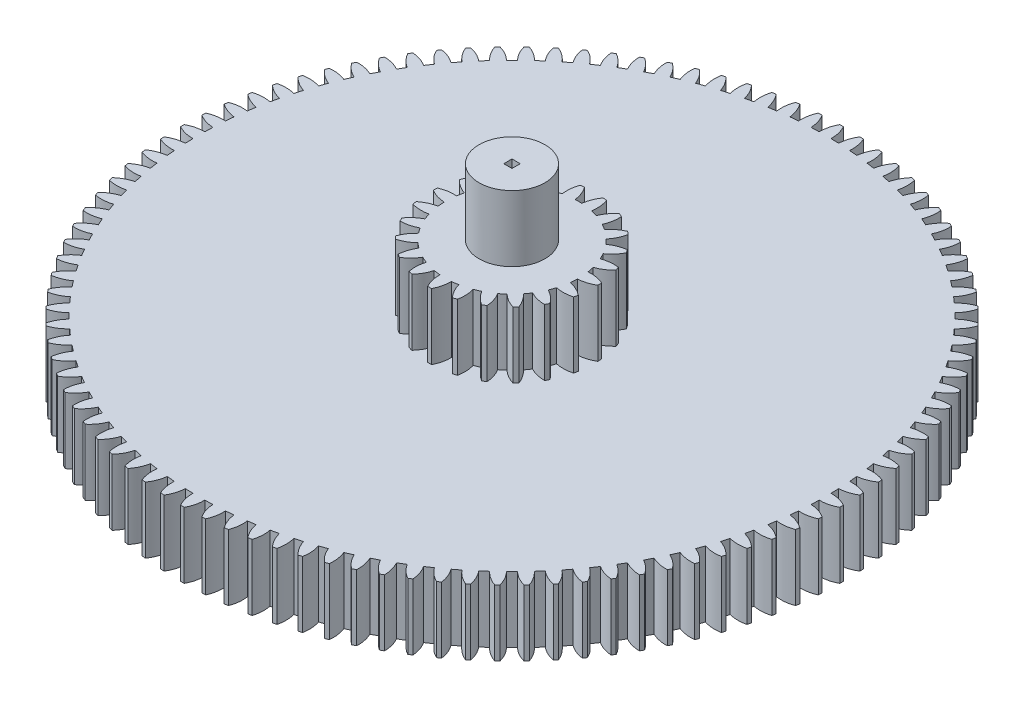
SolidWorks part; units mm, degrees
ref_plane "Front Plane" through (0, 0, 0) normal (0, 0, 1) x (1, 0, 0)
ref_plane "Top Plane" through (0, 0, 0) normal (0, 1, 0) x (1, 0, 0)
ref_plane "Right Plane" through (0, 0, 0) normal (1, 0, 0) x (0, 0, -1)
sketch "Sketch1" plane through (0, 0, 0) normal (0, 1, 0) x (1, 0, 0)
  arc A0 (-1.1228, 2.2337) -> (-1.1773, 2.2054) centre (0, 0) ccw
  arc A1 (-2.1122, 0.8038) -> (-2.1457, 0.7095) centre (0, 0) ccw
  arc A2 (0.05, 2.2594) -> (0.14, 2.4961) centre (0.4546, 2.241) cw
  arc A3 (-0.05, 2.2594) -> (-0.14, 2.4961) centre (-0.4546, 2.241) ccw
  arc A4 (0.3572, 2.2316) -> (0.4786, 2.4538) centre (0.7555, 2.1582) cw
  arc A5 (0.2581, 2.2452) -> (0.2012, 2.4919) centre (-0.1453, 2.282) ccw
  arc A6 (0.6577, 2.1622) -> (0.8082, 2.3657) centre (1.0424, 2.0352) cw
  arc A7 (0.5614, 2.1892) -> (0.5386, 2.4413) centre (0.1668, 2.2805) ccw
  arc A8 (0.946, 2.0525) -> (1.1228, 2.2337) centre (1.3098, 1.8743) cw
  arc A9 (0.8543, 2.0923) -> (0.866, 2.3452) centre (0.4758, 2.2366) ccw
  arc A10 (1.2167, 1.9045) -> (1.4165, 2.06) centre (1.5528, 1.6785) cw
  arc A11 (1.1313, 1.9565) -> (1.1773, 2.2054) centre (0.7759, 2.151) ccw
  arc A12 (1.4647, 1.7211) -> (1.6838, 1.8479) centre (1.7669, 1.4514) cw
  arc A13 (1.3871, 1.7842) -> (1.4666, 2.0246) centre (1.0616, 2.0253) ccw
  arc A14 (1.6854, 1.5057) -> (1.9198, 1.6014) centre (1.9481, 1.1973) cw
  arc A15 (1.6172, 1.5787) -> (1.7287, 1.806) centre (1.3275, 1.8619) ccw
  arc A16 (1.8747, 1.2621) -> (2.12, 1.3251) centre (2.093, 0.9209) cw
  arc A17 (1.8171, 1.3438) -> (1.9585, 1.5538) centre (1.5686, 1.6638) ccw
  arc A18 (2.0291, 0.9951) -> (2.2806, 1.0241) centre (2.1989, 0.6273) cw
  arc A19 (1.9831, 1.0839) -> (2.1518, 1.2727) centre (1.7806, 1.4347) ccw
  arc A20 (2.1457, 0.7095) -> (2.3988, 0.704) centre (2.2638, 0.3221) cw
  arc A21 (2.1122, 0.8038) -> (2.3051, 0.9678) centre (1.9593, 1.1788) ccw
  arc A22 (2.2224, 0.4107) -> (2.4724, 0.3708) centre (2.2866, 0.0108) cw
  arc A23 (2.202, 0.5087) -> (2.4154, 0.6449) centre (2.1016, 0.9011) ccw
  arc A24 (2.2576, 0.1043) -> (2.4998, 0.0307) centre (2.2668, -0.3006) cw
  arc A25 (2.2508, 0.2041) -> (2.4807, 0.31) centre (2.2047, 0.6065) ccw
  arc A26 (2.2508, -0.2041) -> (2.4807, -0.31) centre (2.2047, -0.6065) cw
  arc A27 (2.2576, -0.1043) -> (2.4998, -0.0307) centre (2.2668, 0.3006) ccw
  arc A28 (2.202, -0.5087) -> (2.4154, -0.6449) centre (2.1016, -0.9011) cw
  arc A29 (2.2224, -0.4107) -> (2.4724, -0.3708) centre (2.2866, -0.0108) ccw
  arc A30 (2.1122, -0.8038) -> (2.3051, -0.9678) centre (1.9593, -1.1788) cw
  arc A31 (2.1457, -0.7095) -> (2.3988, -0.704) centre (2.2638, -0.3221) ccw
  arc A32 (1.9831, -1.0839) -> (2.1518, -1.2727) centre (1.7806, -1.4347) cw
  arc A33 (2.0291, -0.9951) -> (2.2806, -1.0241) centre (2.1989, -0.6273) ccw
  arc A34 (1.8171, -1.3438) -> (1.9585, -1.5538) centre (1.5686, -1.6638) cw
  arc A35 (1.8747, -1.2621) -> (2.12, -1.3251) centre (2.093, -0.9209) ccw
  arc A36 (1.6172, -1.5787) -> (1.7287, -1.806) centre (1.3275, -1.8619) cw
  arc A37 (1.6854, -1.5057) -> (1.9198, -1.6014) centre (1.9481, -1.1973) ccw
  arc A38 (1.3871, -1.7842) -> (1.4666, -2.0246) centre (1.0616, -2.0253) cw
  arc A39 (1.4647, -1.7211) -> (1.6838, -1.8479) centre (1.7669, -1.4514) ccw
  arc A40 (1.1313, -1.9565) -> (1.1773, -2.2054) centre (0.7759, -2.151) cw
  arc A41 (1.2167, -1.9045) -> (1.4165, -2.06) centre (1.5528, -1.6785) ccw
  arc A42 (0.8543, -2.0923) -> (0.866, -2.3452) centre (0.4758, -2.2366) cw
  arc A43 (0.946, -2.0525) -> (1.1228, -2.2337) centre (1.3098, -1.8743) ccw
  arc A44 (0.5614, -2.1892) -> (0.5386, -2.4413) centre (0.1668, -2.2805) cw
  arc A45 (0.6577, -2.1622) -> (0.8082, -2.3657) centre (1.0424, -2.0352) ccw
  arc A46 (0.2581, -2.2452) -> (0.2012, -2.4919) centre (-0.1453, -2.282) cw
  arc A47 (0.3572, -2.2316) -> (0.4786, -2.4538) centre (0.7555, -2.1582) ccw
  arc A48 (-0.05, -2.2594) -> (-0.14, -2.4961) centre (-0.4546, -2.241) cw
  arc A49 (0.05, -2.2594) -> (0.14, -2.4961) centre (0.4546, -2.241) ccw
  arc A50 (-0.3572, -2.2316) -> (-0.4786, -2.4538) centre (-0.7555, -2.1582) cw
  arc A51 (-0.2581, -2.2452) -> (-0.2012, -2.4919) centre (0.1453, -2.282) ccw
  arc A52 (-0.6577, -2.1622) -> (-0.8082, -2.3657) centre (-1.0424, -2.0352) cw
  arc A53 (-0.5614, -2.1892) -> (-0.5386, -2.4413) centre (-0.1668, -2.2805) ccw
  arc A54 (-0.946, -2.0525) -> (-1.1228, -2.2337) centre (-1.3098, -1.8743) cw
  arc A55 (-0.8543, -2.0923) -> (-0.866, -2.3452) centre (-0.4758, -2.2366) ccw
  arc A56 (-1.2167, -1.9045) -> (-1.4165, -2.06) centre (-1.5528, -1.6785) cw
  arc A57 (-1.1313, -1.9565) -> (-1.1773, -2.2054) centre (-0.7759, -2.151) ccw
  arc A58 (-1.4647, -1.7211) -> (-1.6838, -1.8479) centre (-1.7669, -1.4514) cw
  arc A59 (-1.3871, -1.7842) -> (-1.4666, -2.0246) centre (-1.0616, -2.0253) ccw
  arc A60 (-1.6854, -1.5057) -> (-1.9198, -1.6014) centre (-1.9481, -1.1973) cw
  arc A61 (-1.6172, -1.5787) -> (-1.7287, -1.806) centre (-1.3275, -1.8619) ccw
  arc A62 (-1.8747, -1.2621) -> (-2.12, -1.3251) centre (-2.093, -0.9209) cw
  arc A63 (-1.8171, -1.3438) -> (-1.9585, -1.5538) centre (-1.5686, -1.6638) ccw
  arc A64 (-2.0291, -0.9951) -> (-2.2806, -1.0241) centre (-2.1989, -0.6273) cw
  arc A65 (-1.9831, -1.0839) -> (-2.1518, -1.2727) centre (-1.7806, -1.4347) ccw
  arc A66 (-2.1457, -0.7095) -> (-2.3988, -0.704) centre (-2.2638, -0.3221) cw
  arc A67 (-2.1122, -0.8038) -> (-2.3051, -0.9678) centre (-1.9593, -1.1788) ccw
  arc A68 (-2.2224, -0.4107) -> (-2.4724, -0.3708) centre (-2.2866, -0.0108) cw
  arc A69 (-2.202, -0.5087) -> (-2.4154, -0.6449) centre (-2.1016, -0.9011) ccw
  arc A70 (-2.2576, -0.1043) -> (-2.4998, -0.0307) centre (-2.2668, 0.3006) cw
  arc A71 (-2.2508, -0.2041) -> (-2.4807, -0.31) centre (-2.2047, -0.6065) ccw
  arc A72 (-2.2508, 0.2041) -> (-2.4807, 0.31) centre (-2.2047, 0.6065) cw
  arc A73 (-2.2576, 0.1043) -> (-2.4998, 0.0307) centre (-2.2668, -0.3006) ccw
  arc A74 (-2.202, 0.5087) -> (-2.4154, 0.6449) centre (-2.1016, 0.9011) cw
  arc A75 (-2.2224, 0.4107) -> (-2.4724, 0.3708) centre (-2.2866, 0.0108) ccw
  arc A76 (-2.1122, 0.8038) -> (-2.3051, 0.9678) centre (-1.9593, 1.1788) cw
  arc A77 (-2.1457, 0.7095) -> (-2.3988, 0.704) centre (-2.2638, 0.3221) ccw
  arc A78 (-1.9831, 1.0839) -> (-2.1518, 1.2727) centre (-1.7806, 1.4347) cw
  arc A79 (-2.0291, 0.9951) -> (-2.2806, 1.0241) centre (-2.1989, 0.6273) ccw
  arc A80 (-1.8171, 1.3438) -> (-1.9585, 1.5538) centre (-1.5686, 1.6638) cw
  arc A81 (-1.8747, 1.2621) -> (-2.12, 1.3251) centre (-2.093, 0.9209) ccw
  arc A82 (-1.6172, 1.5787) -> (-1.7287, 1.806) centre (-1.3275, 1.8619) cw
  arc A83 (-1.6854, 1.5057) -> (-1.9198, 1.6014) centre (-1.9481, 1.1973) ccw
  arc A84 (-1.3871, 1.7842) -> (-1.4666, 2.0246) centre (-1.0616, 2.0253) cw
  arc A85 (-1.4647, 1.7211) -> (-1.6838, 1.8479) centre (-1.7669, 1.4514) ccw
  arc A86 (-1.1313, 1.9565) -> (-1.1773, 2.2054) centre (-0.7759, 2.151) cw
  arc A87 (-1.2167, 1.9045) -> (-1.4165, 2.06) centre (-1.5528, 1.6785) ccw
  arc A88 (-0.8543, 2.0923) -> (-0.866, 2.3452) centre (-0.4758, 2.2366) cw
  arc A89 (-0.946, 2.0525) -> (-1.1228, 2.2337) centre (-1.3098, 1.8743) ccw
  arc A90 (-0.5614, 2.1892) -> (-0.5386, 2.4413) centre (-0.1668, 2.2805) cw
  arc A91 (-0.6577, 2.1622) -> (-0.8082, 2.3657) centre (-1.0424, 2.0352) ccw
  arc A92 (-0.2581, 2.2452) -> (-0.2012, 2.4919) centre (0.1453, 2.282) cw
  arc A93 (-0.3572, 2.2316) -> (-0.4786, 2.4538) centre (-0.7555, 2.1582) ccw
  arc A94 (-1.4165, 2.06) -> (-1.4666, 2.0246) centre (0, 0) ccw
  arc A95 (-1.6838, 1.8479) -> (-1.7287, 1.806) centre (0, 0) ccw
  arc A96 (-1.9198, 1.6014) -> (-1.9585, 1.5538) centre (0, 0) ccw
  arc A97 (-2.12, 1.3251) -> (-2.1518, 1.2727) centre (0, 0) ccw
  arc A98 (-2.2806, 1.0241) -> (-2.3051, 0.9678) centre (0, 0) ccw
  arc A99 (-2.3988, 0.704) -> (-2.4154, 0.6449) centre (0, 0) ccw
  arc A100 (-2.4724, 0.3708) -> (-2.4807, 0.31) centre (0, 0) ccw
  arc A101 (-2.4998, 0.0307) -> (-2.4998, -0.0307) centre (0, 0) ccw
  arc A102 (-2.4807, -0.31) -> (-2.4724, -0.3708) centre (0, 0) ccw
  arc A103 (-2.4154, -0.6449) -> (-2.3988, -0.704) centre (0, 0) ccw
  arc A104 (-2.3051, -0.9678) -> (-2.2806, -1.0241) centre (0, 0) ccw
  arc A105 (-2.1518, -1.2727) -> (-2.12, -1.3251) centre (0, 0) ccw
  arc A106 (-1.9585, -1.5538) -> (-1.9198, -1.6014) centre (0, 0) ccw
  arc A107 (-1.7287, -1.806) -> (-1.6838, -1.8479) centre (0, 0) ccw
  arc A108 (-1.4666, -2.0246) -> (-1.4165, -2.06) centre (0, 0) ccw
  arc A109 (-1.1773, -2.2054) -> (-1.1228, -2.2337) centre (0, 0) ccw
  arc A110 (-0.866, -2.3452) -> (-0.8082, -2.3657) centre (0, 0) ccw
  arc A111 (-0.5386, -2.4413) -> (-0.4786, -2.4538) centre (0, 0) ccw
  arc A112 (-0.2012, -2.4919) -> (-0.14, -2.4961) centre (0, 0) ccw
  arc A113 (0.14, -2.4961) -> (0.2012, -2.4919) centre (0, 0) ccw
  arc A114 (0.4786, -2.4538) -> (0.5386, -2.4413) centre (0, 0) ccw
  arc A115 (0.8082, -2.3657) -> (0.866, -2.3452) centre (0, 0) ccw
  arc A116 (1.1228, -2.2337) -> (1.1773, -2.2054) centre (0, 0) ccw
  arc A117 (1.4165, -2.06) -> (1.4666, -2.0246) centre (0, 0) ccw
  arc A118 (1.6838, -1.8479) -> (1.7287, -1.806) centre (0, 0) ccw
  arc A119 (1.9198, -1.6014) -> (1.9585, -1.5538) centre (0, 0) ccw
  arc A120 (2.12, -1.3251) -> (2.1518, -1.2727) centre (0, 0) ccw
  arc A121 (2.2806, -1.0241) -> (2.3051, -0.9678) centre (0, 0) ccw
  arc A122 (2.3988, -0.704) -> (2.4154, -0.6449) centre (0, 0) ccw
  arc A123 (2.4724, -0.3708) -> (2.4807, -0.31) centre (0, 0) ccw
  arc A124 (2.4998, -0.0307) -> (2.4998, 0.0307) centre (0, 0) ccw
  arc A125 (2.4807, 0.31) -> (2.4724, 0.3708) centre (0, 0) ccw
  arc A126 (2.4154, 0.6449) -> (2.3988, 0.704) centre (0, 0) ccw
  arc A127 (2.3051, 0.9678) -> (2.2806, 1.0241) centre (0, 0) ccw
  arc A128 (2.1518, 1.2727) -> (2.12, 1.3251) centre (0, 0) ccw
  arc A129 (1.9585, 1.5538) -> (1.9198, 1.6014) centre (0, 0) ccw
  arc A130 (1.7287, 1.806) -> (1.6838, 1.8479) centre (0, 0) ccw
  arc A131 (1.4666, 2.0246) -> (1.4165, 2.06) centre (0, 0) ccw
  arc A132 (1.1773, 2.2054) -> (1.1228, 2.2337) centre (0, 0) ccw
  arc A133 (0.866, 2.3452) -> (0.8082, 2.3657) centre (0, 0) ccw
  arc A134 (0.5386, 2.4413) -> (0.4786, 2.4538) centre (0, 0) ccw
  arc A135 (0.2012, 2.4919) -> (0.14, 2.4961) centre (0, 0) ccw
  arc A136 (-0.14, 2.4961) -> (-0.2012, 2.4919) centre (0, 0) ccw
  arc A137 (-0.4786, 2.4538) -> (-0.5386, 2.4413) centre (0, 0) ccw
  arc A138 (-0.8082, 2.3657) -> (-0.866, 2.3452) centre (0, 0) ccw
  arc A139 (-2.202, 0.5087) -> (-2.2224, 0.4107) centre (0, 0) ccw
  arc A140 (-2.2508, 0.2041) -> (-2.2576, 0.1043) centre (0, 0) ccw
  arc A141 (-2.2576, -0.1043) -> (-2.2508, -0.2041) centre (0, 0) ccw
  arc A142 (-2.2224, -0.4107) -> (-2.202, -0.5087) centre (0, 0) ccw
  arc A143 (-2.1457, -0.7095) -> (-2.1122, -0.8038) centre (0, 0) ccw
  arc A144 (-2.0291, -0.9951) -> (-1.9831, -1.0839) centre (0, 0) ccw
  arc A145 (-1.8747, -1.2621) -> (-1.8171, -1.3438) centre (0, 0) ccw
  arc A146 (-1.6854, -1.5057) -> (-1.6172, -1.5787) centre (0, 0) ccw
  arc A147 (-1.4647, -1.7211) -> (-1.3871, -1.7842) centre (0, 0) ccw
  arc A148 (-1.2167, -1.9045) -> (-1.1313, -1.9565) centre (0, 0) ccw
  arc A149 (-0.946, -2.0525) -> (-0.8543, -2.0923) centre (0, 0) ccw
  arc A150 (-0.6577, -2.1622) -> (-0.5614, -2.1892) centre (0, 0) ccw
  arc A151 (-0.3572, -2.2316) -> (-0.2581, -2.2452) centre (0, 0) ccw
  arc A152 (-0.05, -2.2594) -> (0.05, -2.2594) centre (0, 0) ccw
  arc A153 (0.2581, -2.2452) -> (0.3572, -2.2316) centre (0, 0) ccw
  arc A154 (0.5614, -2.1892) -> (0.6577, -2.1622) centre (0, 0) ccw
  arc A155 (0.8543, -2.0923) -> (0.946, -2.0525) centre (0, 0) ccw
  arc A156 (1.1313, -1.9565) -> (1.2167, -1.9045) centre (0, 0) ccw
  arc A157 (1.3871, -1.7842) -> (1.4647, -1.7211) centre (0, 0) ccw
  arc A158 (1.6172, -1.5787) -> (1.6854, -1.5057) centre (0, 0) ccw
  arc A159 (1.8171, -1.3438) -> (1.8747, -1.2621) centre (0, 0) ccw
  arc A160 (1.9831, -1.0839) -> (2.0291, -0.9951) centre (0, 0) ccw
  arc A161 (2.1122, -0.8038) -> (2.1457, -0.7095) centre (0, 0) ccw
  arc A162 (2.202, -0.5087) -> (2.2224, -0.4107) centre (0, 0) ccw
  arc A163 (2.2508, -0.2041) -> (2.2576, -0.1043) centre (0, 0) ccw
  arc A164 (2.2576, 0.1043) -> (2.2508, 0.2041) centre (0, 0) ccw
  arc A165 (2.2224, 0.4107) -> (2.202, 0.5087) centre (0, 0) ccw
  arc A166 (2.1457, 0.7095) -> (2.1122, 0.8038) centre (0, 0) ccw
  arc A167 (2.0291, 0.9951) -> (1.9831, 1.0839) centre (0, 0) ccw
  arc A168 (1.8747, 1.2621) -> (1.8171, 1.3438) centre (0, 0) ccw
  arc A169 (1.6854, 1.5057) -> (1.6172, 1.5787) centre (0, 0) ccw
  arc A170 (1.4647, 1.7211) -> (1.3871, 1.7842) centre (0, 0) ccw
  arc A171 (1.2167, 1.9045) -> (1.1313, 1.9565) centre (0, 0) ccw
  arc A172 (0.946, 2.0525) -> (0.8543, 2.0923) centre (0, 0) ccw
  arc A173 (0.6577, 2.1622) -> (0.5614, 2.1892) centre (0, 0) ccw
  arc A174 (0.3572, 2.2316) -> (0.2581, 2.2452) centre (0, 0) ccw
  arc A175 (0.05, 2.2594) -> (-0.05, 2.2594) centre (0, 0) ccw
  arc A176 (-1.3871, 1.7842) -> (-1.4647, 1.7211) centre (0, 0) ccw
  arc A177 (-1.1313, 1.9565) -> (-1.2167, 1.9045) centre (0, 0) ccw
  arc A178 (-0.8543, 2.0923) -> (-0.946, 2.0525) centre (0, 0) ccw
  arc A179 (-0.5614, 2.1892) -> (-0.6577, 2.1622) centre (0, 0) ccw
  arc A180 (-0.2581, 2.2452) -> (-0.3572, 2.2316) centre (0, 0) ccw
  arc A181 (-1.6172, 1.5787) -> (-1.6854, 1.5057) centre (0, 0) ccw
  arc A182 (-1.8171, 1.3438) -> (-1.8747, 1.2621) centre (0, 0) ccw
  arc A183 (-1.9831, 1.0839) -> (-2.0291, 0.9951) centre (0, 0) ccw
  point P4 (0, 2.26)
  point P5 (0, 2.5)
  point P285 (0, 0)
  dimension "D1" = 5
  dimension "D2" = 0.24
  dimension "D5" = 46
extrude "Boss-Extrude1" add sketch "Sketch1" along normal blind 1
sketch "Sketch2" plane through (0, 0, 0) normal (0, -1, 0) x (1, 0, 0)
  circle A0 centre (0, 0) radius 0.5
  dimension "D1" = 1
extrude "Boss-Extrude2" add sketch "Sketch2" along normal blind 2 and the other way blind 3
sketch "Sketch3" plane through (0, 1, 0) normal (0, 1, 0) x (1, 0, 0)
  arc A0 (-0.765, 0.9886) -> (-0.8122, 0.9501) centre (0, 0) ccw
  arc A1 (-0.4814, 0.8879) -> (-0.5669, 0.8359) centre (0, 0) ccw
  arc A2 (0.05, 1.0088) -> (0.14, 1.2421) centre (0.5621, 0.9453) cw
  arc A3 (-0.05, 1.0088) -> (-0.14, 1.2421) centre (-0.5621, 0.9453) ccw
  arc A4 (0.3203, 0.9579) -> (0.4699, 1.1583) centre (0.7963, 0.7586) cw
  arc A5 (0.224, 0.9848) -> (0.2003, 1.2338) centre (-0.2862, 1.0619) ccw
  arc A6 (0.5669, 0.8359) -> (0.765, 0.9886) centre (0.9714, 0.5157) cw
  arc A7 (0.4814, 0.8879) -> (0.5258, 1.134) centre (0.0109, 1.0997) ccw
  arc A8 (0.7714, 0.652) -> (1.0034, 0.7455) centre (1.0745, 0.2345) cw
  arc A9 (0.7031, 0.7251) -> (0.8122, 0.9501) centre (0.3072, 1.056) ccw
  arc A10 (0.9187, 0.4197) -> (1.1673, 0.4472) centre (1.0979, -0.0641) cw
  arc A11 (0.8727, 0.5085) -> (1.0385, 0.6958) centre (0.5808, 0.934) ccw
  arc A12 (0.9978, 0.1563) -> (1.2446, 0.1156) centre (1.0399, -0.358) cw
  arc A13 (0.9775, 0.2542) -> (1.1877, 0.3898) centre (0.8112, 0.7426) ccw
  arc A14 (1.003, -0.1187) -> (1.2297, -0.2244) centre (0.9048, -0.6253) cw
  arc A15 (1.0098, -0.019) -> (1.2488, 0.0549) centre (0.9815, 0.4962) ccw
  arc A16 (0.9338, -0.3849) -> (1.1235, -0.5479) centre (0.7025, -0.8462) cw
  arc A17 (0.9673, -0.2907) -> (1.2173, -0.284) centre (1.079, 0.213) ccw
  arc A18 (0.7953, -0.6226) -> (0.9341, -0.8307) centre (0.4482, -1.0043) cw
  arc A19 (0.853, -0.5409) -> (1.0955, -0.6019) centre (1.0964, -0.086) ccw
  arc A20 (0.5978, -0.8141) -> (0.6753, -1.0519) centre (0.1606, -1.088) cw
  arc A21 (0.6754, -0.751) -> (0.8925, -0.8752) centre (1.0326, -0.3786) ccw
  arc A22 (0.356, -0.9452) -> (0.3665, -1.1951) centre (-0.1389, -1.091) cw
  arc A23 (0.4478, -0.9053) -> (0.6233, -1.0835) centre (0.8922, -0.6431) ccw
  arc A24 (0.0878, -1.0062) -> (0.0304, -1.2496) centre (-0.4281, -1.0131) cw
  arc A25 (0.1869, -0.9926) -> (0.3078, -1.2115) centre (0.6856, -0.86) ccw
  arc A26 (-0.1869, -0.9926) -> (-0.3078, -1.2115) centre (-0.6856, -0.86) cw
  arc A27 (-0.0878, -1.0062) -> (-0.0304, -1.2496) centre (0.4281, -1.0131) ccw
  arc A28 (-0.4478, -0.9053) -> (-0.6233, -1.0835) centre (-0.8922, -0.6431) cw
  arc A29 (-0.356, -0.9452) -> (-0.3665, -1.1951) centre (0.1389, -1.091) ccw
  arc A30 (-0.6754, -0.751) -> (-0.8925, -0.8752) centre (-1.0326, -0.3786) cw
  arc A31 (-0.5978, -0.8141) -> (-0.6753, -1.0519) centre (-0.1606, -1.088) ccw
  arc A32 (-0.853, -0.5409) -> (-1.0955, -0.6019) centre (-1.0964, -0.086) cw
  arc A33 (-0.7953, -0.6226) -> (-0.9341, -0.8307) centre (-0.4482, -1.0043) ccw
  arc A34 (-0.9673, -0.2907) -> (-1.2173, -0.284) centre (-1.079, 0.213) cw
  arc A35 (-0.9338, -0.3849) -> (-1.1235, -0.5479) centre (-0.7025, -0.8462) ccw
  arc A36 (-1.0098, -0.019) -> (-1.2488, 0.0549) centre (-0.9815, 0.4962) cw
  arc A37 (-1.003, -0.1187) -> (-1.2297, -0.2244) centre (-0.9048, -0.6253) ccw
  arc A38 (-0.9775, 0.2542) -> (-1.1877, 0.3898) centre (-0.8112, 0.7426) cw
  arc A39 (-0.9978, 0.1563) -> (-1.2446, 0.1156) centre (-1.0399, -0.358) ccw
  arc A40 (-0.8727, 0.5085) -> (-1.0385, 0.6958) centre (-0.5808, 0.934) cw
  arc A41 (-0.9187, 0.4197) -> (-1.1673, 0.4472) centre (-1.0979, -0.0641) ccw
  arc A42 (-0.7031, 0.7251) -> (-0.8122, 0.9501) centre (-0.3072, 1.056) cw
  arc A43 (-0.7714, 0.652) -> (-1.0034, 0.7455) centre (-1.0745, 0.2345) ccw
  arc A44 (-0.4814, 0.8879) -> (-0.5258, 1.134) centre (-0.0109, 1.0997) cw
  arc A45 (-0.5669, 0.8359) -> (-0.765, 0.9886) centre (-0.9714, 0.5157) ccw
  arc A46 (-0.224, 0.9848) -> (-0.2003, 1.2338) centre (0.2862, 1.0619) cw
  arc A47 (-0.3203, 0.9579) -> (-0.4699, 1.1583) centre (-0.7963, 0.7586) ccw
  arc A48 (-1.0034, 0.7455) -> (-1.0385, 0.6958) centre (0, 0) ccw
  arc A49 (-1.2446, 0.1156) -> (-1.2488, 0.0549) centre (0, 0) ccw
  arc A50 (-1.1673, 0.4472) -> (-1.1877, 0.3898) centre (0, 0) ccw
  arc A51 (-1.2297, -0.2244) -> (-1.2173, -0.284) centre (0, 0) ccw
  arc A52 (-1.1235, -0.5479) -> (-1.0955, -0.6019) centre (0, 0) ccw
  arc A53 (-0.9341, -0.8307) -> (-0.8925, -0.8752) centre (0, 0) ccw
  arc A54 (-0.3665, -1.1951) -> (-0.3078, -1.2115) centre (0, 0) ccw
  arc A55 (-0.6753, -1.0519) -> (-0.6233, -1.0835) centre (0, 0) ccw
  arc A56 (-0.0304, -1.2496) -> (0.0304, -1.2496) centre (0, 0) ccw
  arc A57 (0.6233, -1.0835) -> (0.6753, -1.0519) centre (0, 0) ccw
  arc A58 (0.8925, -0.8752) -> (0.9341, -0.8307) centre (0, 0) ccw
  arc A59 (0.3078, -1.2115) -> (0.3665, -1.1951) centre (0, 0) ccw
  arc A60 (1.2173, -0.284) -> (1.2297, -0.2244) centre (0, 0) ccw
  arc A61 (1.0955, -0.6019) -> (1.1235, -0.5479) centre (0, 0) ccw
  arc A62 (1.2488, 0.0549) -> (1.2446, 0.1156) centre (0, 0) ccw
  arc A63 (1.1877, 0.3898) -> (1.1673, 0.4472) centre (0, 0) ccw
  arc A64 (1.0385, 0.6958) -> (1.0034, 0.7455) centre (0, 0) ccw
  arc A65 (0.8122, 0.9501) -> (0.765, 0.9886) centre (0, 0) ccw
  arc A66 (0.5258, 1.134) -> (0.4699, 1.1583) centre (0, 0) ccw
  arc A67 (0.2003, 1.2338) -> (0.14, 1.2421) centre (0, 0) ccw
  arc A68 (-0.4699, 1.1583) -> (-0.5258, 1.134) centre (0, 0) ccw
  arc A69 (-0.14, 1.2421) -> (-0.2003, 1.2338) centre (0, 0) ccw
  arc A70 (-0.7031, 0.7251) -> (-0.7714, 0.652) centre (0, 0) ccw
  arc A71 (-0.9775, 0.2542) -> (-0.9978, 0.1563) centre (0, 0) ccw
  arc A72 (-1.0098, -0.019) -> (-1.003, -0.1187) centre (0, 0) ccw
  arc A73 (-0.9673, -0.2907) -> (-0.9338, -0.3849) centre (0, 0) ccw
  arc A74 (-0.853, -0.5409) -> (-0.7953, -0.6226) centre (0, 0) ccw
  arc A75 (-0.224, 0.9848) -> (-0.3203, 0.9579) centre (0, 0) ccw
  arc A76 (0.05, 1.0088) -> (-0.05, 1.0088) centre (0, 0) ccw
  arc A77 (0.3203, 0.9579) -> (0.224, 0.9848) centre (0, 0) ccw
  arc A78 (0.5669, 0.8359) -> (0.4814, 0.8879) centre (0, 0) ccw
  arc A79 (0.7714, 0.652) -> (0.7031, 0.7251) centre (0, 0) ccw
  arc A80 (0.9187, 0.4197) -> (0.8727, 0.5085) centre (0, 0) ccw
  arc A81 (0.9978, 0.1563) -> (0.9775, 0.2542) centre (0, 0) ccw
  arc A82 (1.003, -0.1187) -> (1.0098, -0.019) centre (0, 0) ccw
  arc A83 (0.9338, -0.3849) -> (0.9673, -0.2907) centre (0, 0) ccw
  arc A84 (0.7953, -0.6226) -> (0.853, -0.5409) centre (0, 0) ccw
  arc A85 (0.5978, -0.8141) -> (0.6754, -0.751) centre (0, 0) ccw
  arc A86 (0.356, -0.9452) -> (0.4478, -0.9053) centre (0, 0) ccw
  arc A87 (0.0878, -1.0062) -> (0.1869, -0.9926) centre (0, 0) ccw
  arc A88 (-0.1869, -0.9926) -> (-0.0878, -1.0062) centre (0, 0) ccw
  arc A89 (-0.4478, -0.9053) -> (-0.356, -0.9452) centre (0, 0) ccw
  arc A90 (-0.6754, -0.751) -> (-0.5978, -0.8141) centre (0, 0) ccw
  arc A91 (-0.8727, 0.5085) -> (-0.9187, 0.4197) centre (0, 0) ccw
  point P4 (0, 1.25)
  point P5 (0, 1.01)
  point P147 (0, 0)
  dimension "D1" = 2.5
  dimension "D2" = 0.24
  dimension "D5" = 23
extrude "Boss-Extrude3" add sketch "Sketch3" along normal blind 1 contours A30 A90 A31 A55 A28 A89 A29 A54 A26 A88 A27 A56 A24 A87 A25 A59 A22 A86 A23 A57 A20 A85 A21 A58 A18 A84 A19 A61 A16 A83 A17 A60 A14 A82 A15 A62 A12 A81 A13 A63 A10 A80 A11 A64 A8 A79 A9 A65 A6 A78 A7 region at (0, 1, 0)
scale "Scale1" bodies to scale 103 scale about origin uniform scaling yes scale factor 2
sketch "Sketch4" plane through (0, 6, 0) normal (0, 1, 0) x (1, 0, 0)
  line L1 (-0.125, -0.125) -> (0.125, -0.125)
  line L2 (-0.125, -0.125) -> (-0.125, 0.125)
  line L3 (-0.125, 0.125) -> (0.125, 0.125)
  line L4 (0.125, -0.125) -> (0.125, 0.125)
  line L5 (-0.125, -0.125) -> (0.125, 0.125) construction
  line L6 (-0.125, 0.125) -> (0.125, -0.125) construction
  point P0 (0, 0)
  dimension "D1" = 0.25
  dimension "D2" = 0.25
extrude "Cut-Extrude1" cut sketch "Sketch4" against normal blind 1
sketch "Sketch5" plane through (0, -4, 0) normal (0, -1, 0) x (1, 0, 0)
  circle A0 centre (0, 0) radius 1
extrude "Cut-Extrude2" cut sketch "Sketch5" against normal blind 1.4
sketch "Sketch6" plane through (0, 0, 0) normal (0, -1, 0) x (1, 0, 0)
  circle A0 centre (0, 0) radius 1
  circle A1 centre (0, 0) radius 5
  dimension "D1" = 10
extrude "Cut-Extrude3" cut sketch "Sketch6" against normal blind 2
sketch "Sketch8" plane through (0, 2, 0) normal (0, -1, 0) x (1, 0, 0)
  line L0 (0, 0) -> (0, 0.18) construction
  line L1 (0, 0.18) -> (9.4983, 0.18) construction
  line L2 (0, 0) -> (0, -0.18) construction
  line L3 (0, -0.18) -> (9.4983, -0.18) construction
  arc A0 (9.9998, -0.0563) -> (9.9998, 0.0563) centre (0, 0) ccw
  arc A1 (9.4983, 0.18) -> (9.4909, 0.4168) centre (0, 0) ccw
  arc A2 (9.9998, 0.0563) -> (9.4983, 0.18) centre (9.5098, -0.8519) ccw
  arc A3 (9.9998, -0.0563) -> (9.4983, -0.18) centre (9.5098, 0.8519) cw
  arc A4 (9.9836, -0.5717) -> (9.4909, -0.4168) centre (9.4375, -1.4473) ccw
  arc A5 (9.9766, -0.6841) -> (9.9836, -0.5717) centre (0, 0) ccw
  arc A6 (9.9766, -0.6841) -> (9.4682, -0.776) centre (9.5445, 0.2531) cw
  arc A7 (9.928, -1.1975) -> (9.446, -1.0119) centre (9.328, -2.0371) ccw
  arc A8 (9.9139, -1.3091) -> (9.928, -1.1975) centre (0, 0) ccw
  arc A9 (9.9139, -1.3091) -> (9.4008, -1.369) centre (9.5416, -0.3467) cw
  arc A10 (9.8333, -1.8185) -> (9.3638, -1.603) centre (9.1817, -2.6188) ccw
  arc A11 (9.8122, -1.9291) -> (9.8333, -1.8185) centre (0, 0) ccw
  arc A12 (9.8122, -1.9291) -> (9.2963, -1.9566) centre (9.501, -0.9452) cw
  arc A13 (9.6997, -2.4324) -> (9.2447, -2.1878) centre (8.9991, -3.1901) ccw
  arc A14 (9.6717, -2.5414) -> (9.6997, -2.4324) centre (0, 0) ccw
  arc A15 (9.6717, -2.5414) -> (9.1551, -2.5365) centre (9.4229, -1.5399) cw
  arc A16 (9.5278, -3.0366) -> (9.089, -2.7639) centre (8.7811, -3.7489) ccw
  arc A17 (9.493, -3.1436) -> (9.5278, -3.0366) centre (0, 0) ccw
  arc A18 (9.493, -3.1436) -> (8.9778, -3.1063) centre (9.3076, -2.1285) cw
  arc A19 (9.3183, -3.6289) -> (8.8976, -3.3292) centre (8.5284, -4.2929) ccw
  arc A20 (9.2769, -3.7335) -> (9.3183, -3.6289) centre (0, 0) ccw
  arc A21 (9.2769, -3.7335) -> (8.765, -3.6639) centre (9.1556, -2.7087) cw
  arc A22 (9.0721, -4.2068) -> (8.671, -3.8813) centre (8.242, -4.8199) ccw
  arc A23 (9.0242, -4.3086) -> (9.0721, -4.2068) centre (0, 0) ccw
  arc A24 (9.0242, -4.3086) -> (8.5177, -4.207) centre (8.9674, -3.2782) cw
  arc A25 (8.79, -4.7681) -> (8.4101, -4.4181) centre (7.9231, -5.3279) ccw
  arc A26 (8.7358, -4.8668) -> (8.79, -4.7681) centre (0, 0) ccw
  arc A27 (8.7358, -4.8668) -> (8.2367, -4.7336) centre (8.7439, -3.8348) cw
  arc A28 (8.4733, -5.3107) -> (8.1161, -4.9375) centre (7.5729, -5.8149) ccw
  arc A29 (8.413, -5.4057) -> (8.4733, -5.3107) centre (0, 0) ccw
  arc A30 (8.413, -5.4057) -> (7.9232, -5.2414) centre (8.4858, -4.3763) cw
  arc A31 (8.1231, -5.8322) -> (7.7901, -5.4373) centre (7.1928, -6.2789) ccw
  arc A32 (8.057, -5.9233) -> (8.1231, -5.8322) centre (0, 0) ccw
  arc A33 (8.057, -5.9233) -> (7.5785, -5.7286) centre (8.1943, -4.9005) cw
  arc A34 (7.7409, -6.3308) -> (7.4333, -5.9157) centre (6.7844, -6.7182) ccw
  arc A35 (7.6691, -6.4175) -> (7.7409, -6.3308) centre (0, 0) ccw
  arc A36 (7.6691, -6.4175) -> (7.2038, -6.1931) centre (7.8704, -5.4054) cw
  arc A37 (7.3281, -6.8043) -> (7.0472, -6.3708) centre (6.3492, -7.1309) ccw
  arc A38 (7.251, -6.8864) -> (7.3281, -6.8043) centre (0, 0) ccw
  arc A39 (7.251, -6.8864) -> (6.8007, -6.6332) centre (7.5155, -5.8889) cw
  arc A40 (6.8864, -7.251) -> (6.6332, -6.8007) centre (5.8889, -7.5155) ccw
  arc A41 (6.8043, -7.3281) -> (6.8864, -7.251) centre (0, 0) ccw
  arc A42 (6.8043, -7.3281) -> (6.3708, -7.0472) centre (7.1309, -6.3492) cw
  arc A43 (6.4175, -7.6691) -> (6.1931, -7.2038) centre (5.4054, -7.8704) ccw
  arc A44 (6.3308, -7.7409) -> (6.4175, -7.6691) centre (0, 0) ccw
  arc A45 (6.3308, -7.7409) -> (5.9157, -7.4333) centre (6.7182, -6.7844) cw
  arc A46 (5.9233, -8.057) -> (5.7286, -7.5785) centre (4.9005, -8.1943) ccw
  arc A47 (5.8322, -8.1231) -> (5.9233, -8.057) centre (0, 0) ccw
  arc A48 (5.8322, -8.1231) -> (5.4373, -7.7901) centre (6.2789, -7.1928) cw
  arc A49 (5.4057, -8.413) -> (5.2414, -7.9232) centre (4.3763, -8.4858) ccw
  arc A50 (5.3107, -8.4733) -> (5.4057, -8.413) centre (0, 0) ccw
  arc A51 (5.3107, -8.4733) -> (4.9375, -8.1161) centre (5.8149, -7.5729) cw
  arc A52 (4.8668, -8.7358) -> (4.7336, -8.2367) centre (3.8348, -8.7439) ccw
  arc A53 (4.7681, -8.79) -> (4.8668, -8.7358) centre (0, 0) ccw
  arc A54 (4.7681, -8.79) -> (4.4181, -8.4101) centre (5.3279, -7.9231) cw
  arc A55 (4.3086, -9.0242) -> (4.207, -8.5177) centre (3.2782, -8.9674) ccw
  arc A56 (4.2068, -9.0721) -> (4.3086, -9.0242) centre (0, 0) ccw
  arc A57 (4.2068, -9.0721) -> (3.8813, -8.671) centre (4.8199, -8.242) cw
  arc A58 (3.7335, -9.2769) -> (3.6639, -8.765) centre (2.7087, -9.1556) ccw
  arc A59 (3.6289, -9.3183) -> (3.7335, -9.2769) centre (0, 0) ccw
  arc A60 (3.6289, -9.3183) -> (3.3292, -8.8976) centre (4.2929, -8.5284) cw
  arc A61 (3.1436, -9.493) -> (3.1063, -8.9778) centre (2.1285, -9.3076) ccw
  arc A62 (3.0366, -9.5278) -> (3.1436, -9.493) centre (0, 0) ccw
  arc A63 (3.0366, -9.5278) -> (2.7639, -9.089) centre (3.7489, -8.7811) cw
  arc A64 (2.5414, -9.6717) -> (2.5365, -9.1551) centre (1.5399, -9.4229) ccw
  arc A65 (2.4324, -9.6997) -> (2.5414, -9.6717) centre (0, 0) ccw
  arc A66 (2.4324, -9.6997) -> (2.1878, -9.2447) centre (3.1901, -8.9991) cw
  arc A67 (1.9291, -9.8122) -> (1.9566, -9.2963) centre (0.9452, -9.501) ccw
  arc A68 (1.8185, -9.8333) -> (1.9291, -9.8122) centre (0, 0) ccw
  arc A69 (1.8185, -9.8333) -> (1.603, -9.3638) centre (2.6188, -9.1817) cw
  arc A70 (1.3091, -9.9139) -> (1.369, -9.4008) centre (0.3467, -9.5416) ccw
  arc A71 (1.1975, -9.928) -> (1.3091, -9.9139) centre (0, 0) ccw
  arc A72 (1.1975, -9.928) -> (1.0119, -9.446) centre (2.0371, -9.328) cw
  arc A73 (0.6841, -9.9766) -> (0.776, -9.4682) centre (-0.2531, -9.5445) ccw
  arc A74 (0.5717, -9.9836) -> (0.6841, -9.9766) centre (0, 0) ccw
  arc A75 (0.5717, -9.9836) -> (0.4168, -9.4909) centre (1.4473, -9.4375) cw
  arc A76 (0.0563, -9.9998) -> (0.18, -9.4983) centre (-0.8519, -9.5098) ccw
  arc A77 (-0.0563, -9.9998) -> (0.0563, -9.9998) centre (0, 0) ccw
  arc A78 (-0.0563, -9.9998) -> (-0.18, -9.4983) centre (0.8519, -9.5098) cw
  arc A79 (-0.5717, -9.9836) -> (-0.4168, -9.4909) centre (-1.4473, -9.4375) ccw
  arc A80 (-0.6841, -9.9766) -> (-0.5717, -9.9836) centre (0, 0) ccw
  arc A81 (-0.6841, -9.9766) -> (-0.776, -9.4682) centre (0.2531, -9.5445) cw
  arc A82 (-1.1975, -9.928) -> (-1.0119, -9.446) centre (-2.0371, -9.328) ccw
  arc A83 (-1.3091, -9.9139) -> (-1.1975, -9.928) centre (0, 0) ccw
  arc A84 (-1.3091, -9.9139) -> (-1.369, -9.4008) centre (-0.3467, -9.5416) cw
  arc A85 (-1.8185, -9.8333) -> (-1.603, -9.3638) centre (-2.6188, -9.1817) ccw
  arc A86 (-1.9291, -9.8122) -> (-1.8185, -9.8333) centre (0, 0) ccw
  arc A87 (-1.9291, -9.8122) -> (-1.9566, -9.2963) centre (-0.9452, -9.501) cw
  arc A88 (-2.4324, -9.6997) -> (-2.1878, -9.2447) centre (-3.1901, -8.9991) ccw
  arc A89 (-2.5414, -9.6717) -> (-2.4324, -9.6997) centre (0, 0) ccw
  arc A90 (-2.5414, -9.6717) -> (-2.5365, -9.1551) centre (-1.5399, -9.4229) cw
  arc A91 (-3.0366, -9.5278) -> (-2.7639, -9.089) centre (-3.7489, -8.7811) ccw
  arc A92 (-3.1436, -9.493) -> (-3.0366, -9.5278) centre (0, 0) ccw
  arc A93 (-3.1436, -9.493) -> (-3.1063, -8.9778) centre (-2.1285, -9.3076) cw
  arc A94 (-3.6289, -9.3183) -> (-3.3292, -8.8976) centre (-4.2929, -8.5284) ccw
  arc A95 (-3.7335, -9.2769) -> (-3.6289, -9.3183) centre (0, 0) ccw
  arc A96 (-3.7335, -9.2769) -> (-3.6639, -8.765) centre (-2.7087, -9.1556) cw
  arc A97 (-4.2068, -9.0721) -> (-3.8813, -8.671) centre (-4.8199, -8.242) ccw
  arc A98 (-4.3086, -9.0242) -> (-4.2068, -9.0721) centre (0, 0) ccw
  arc A99 (-4.3086, -9.0242) -> (-4.207, -8.5177) centre (-3.2782, -8.9674) cw
  arc A100 (-4.7681, -8.79) -> (-4.4181, -8.4101) centre (-5.3279, -7.9231) ccw
  arc A101 (-4.8668, -8.7358) -> (-4.7681, -8.79) centre (0, 0) ccw
  arc A102 (-4.8668, -8.7358) -> (-4.7336, -8.2367) centre (-3.8348, -8.7439) cw
  arc A103 (-5.3107, -8.4733) -> (-4.9375, -8.1161) centre (-5.8149, -7.5729) ccw
  arc A104 (-5.4057, -8.413) -> (-5.3107, -8.4733) centre (0, 0) ccw
  arc A105 (-5.4057, -8.413) -> (-5.2414, -7.9232) centre (-4.3763, -8.4858) cw
  arc A106 (-5.8322, -8.1231) -> (-5.4373, -7.7901) centre (-6.2789, -7.1928) ccw
  arc A107 (-5.9233, -8.057) -> (-5.8322, -8.1231) centre (0, 0) ccw
  arc A108 (-5.9233, -8.057) -> (-5.7286, -7.5785) centre (-4.9005, -8.1943) cw
  arc A109 (-6.3308, -7.7409) -> (-5.9157, -7.4333) centre (-6.7182, -6.7844) ccw
  arc A110 (-6.4175, -7.6691) -> (-6.3308, -7.7409) centre (0, 0) ccw
  arc A111 (-6.4175, -7.6691) -> (-6.1931, -7.2038) centre (-5.4054, -7.8704) cw
  arc A112 (-6.8043, -7.3281) -> (-6.3708, -7.0472) centre (-7.1309, -6.3492) ccw
  arc A113 (-6.8864, -7.251) -> (-6.8043, -7.3281) centre (0, 0) ccw
  arc A114 (-6.8864, -7.251) -> (-6.6332, -6.8007) centre (-5.8889, -7.5155) cw
  arc A115 (-7.251, -6.8864) -> (-6.8007, -6.6332) centre (-7.5155, -5.8889) ccw
  arc A116 (-7.3281, -6.8043) -> (-7.251, -6.8864) centre (0, 0) ccw
  arc A117 (-7.3281, -6.8043) -> (-7.0472, -6.3708) centre (-6.3492, -7.1309) cw
  arc A118 (-7.6691, -6.4175) -> (-7.2038, -6.1931) centre (-7.8704, -5.4054) ccw
  arc A119 (-7.7409, -6.3308) -> (-7.6691, -6.4175) centre (0, 0) ccw
  arc A120 (-7.7409, -6.3308) -> (-7.4333, -5.9157) centre (-6.7844, -6.7182) cw
  arc A121 (-8.057, -5.9233) -> (-7.5785, -5.7286) centre (-8.1943, -4.9005) ccw
  arc A122 (-8.1231, -5.8322) -> (-8.057, -5.9233) centre (0, 0) ccw
  arc A123 (-8.1231, -5.8322) -> (-7.7901, -5.4373) centre (-7.1928, -6.2789) cw
  arc A124 (-8.413, -5.4057) -> (-7.9232, -5.2414) centre (-8.4858, -4.3763) ccw
  arc A125 (-8.4733, -5.3107) -> (-8.413, -5.4057) centre (0, 0) ccw
  arc A126 (-8.4733, -5.3107) -> (-8.1161, -4.9375) centre (-7.5729, -5.8149) cw
  arc A127 (-8.7358, -4.8668) -> (-8.2367, -4.7336) centre (-8.7439, -3.8348) ccw
  arc A128 (-8.79, -4.7681) -> (-8.7358, -4.8668) centre (0, 0) ccw
  arc A129 (-8.79, -4.7681) -> (-8.4101, -4.4181) centre (-7.9231, -5.3279) cw
  arc A130 (-9.0242, -4.3086) -> (-8.5177, -4.207) centre (-8.9674, -3.2782) ccw
  arc A131 (-9.0721, -4.2068) -> (-9.0242, -4.3086) centre (0, 0) ccw
  arc A132 (-9.0721, -4.2068) -> (-8.671, -3.8813) centre (-8.242, -4.8199) cw
  arc A133 (-9.2769, -3.7335) -> (-8.765, -3.6639) centre (-9.1556, -2.7087) ccw
  arc A134 (-9.3183, -3.6289) -> (-9.2769, -3.7335) centre (0, 0) ccw
  arc A135 (-9.3183, -3.6289) -> (-8.8976, -3.3292) centre (-8.5284, -4.2929) cw
  arc A136 (-9.493, -3.1436) -> (-8.9778, -3.1063) centre (-9.3076, -2.1285) ccw
  arc A137 (-9.5278, -3.0366) -> (-9.493, -3.1436) centre (0, 0) ccw
  arc A138 (-9.5278, -3.0366) -> (-9.089, -2.7639) centre (-8.7811, -3.7489) cw
  arc A139 (-9.6717, -2.5414) -> (-9.1551, -2.5365) centre (-9.4229, -1.5399) ccw
  arc A140 (-9.6997, -2.4324) -> (-9.6717, -2.5414) centre (0, 0) ccw
  arc A141 (-9.6997, -2.4324) -> (-9.2447, -2.1878) centre (-8.9991, -3.1901) cw
  arc A142 (-9.8122, -1.9291) -> (-9.2963, -1.9566) centre (-9.501, -0.9452) ccw
  arc A143 (-9.8333, -1.8185) -> (-9.8122, -1.9291) centre (0, 0) ccw
  arc A144 (-9.8333, -1.8185) -> (-9.3638, -1.603) centre (-9.1817, -2.6188) cw
  arc A145 (-9.9139, -1.3091) -> (-9.4008, -1.369) centre (-9.5416, -0.3467) ccw
  arc A146 (-9.928, -1.1975) -> (-9.9139, -1.3091) centre (0, 0) ccw
  arc A147 (-9.928, -1.1975) -> (-9.446, -1.0119) centre (-9.328, -2.0371) cw
  arc A148 (-9.9766, -0.6841) -> (-9.4682, -0.776) centre (-9.5445, 0.2531) ccw
  arc A149 (-9.9836, -0.5717) -> (-9.9766, -0.6841) centre (0, 0) ccw
  arc A150 (-9.9836, -0.5717) -> (-9.4909, -0.4168) centre (-9.4375, -1.4473) cw
  arc A151 (-9.9998, -0.0563) -> (-9.4983, -0.18) centre (-9.5098, 0.8519) ccw
  arc A152 (-9.9998, 0.0563) -> (-9.9998, -0.0563) centre (0, 0) ccw
  arc A153 (-9.9998, 0.0563) -> (-9.4983, 0.18) centre (-9.5098, -0.8519) cw
  arc A154 (-9.9836, 0.5717) -> (-9.4909, 0.4168) centre (-9.4375, 1.4473) ccw
  arc A155 (-9.9766, 0.6841) -> (-9.9836, 0.5717) centre (0, 0) ccw
  arc A156 (-9.9766, 0.6841) -> (-9.4682, 0.776) centre (-9.5445, -0.2531) cw
  arc A157 (-9.928, 1.1975) -> (-9.446, 1.0119) centre (-9.328, 2.0371) ccw
  arc A158 (-9.9139, 1.3091) -> (-9.928, 1.1975) centre (0, 0) ccw
  arc A159 (-9.9139, 1.3091) -> (-9.4008, 1.369) centre (-9.5416, 0.3467) cw
  arc A160 (-9.8333, 1.8185) -> (-9.3638, 1.603) centre (-9.1817, 2.6188) ccw
  arc A161 (-9.8122, 1.9291) -> (-9.8333, 1.8185) centre (0, 0) ccw
  arc A162 (-9.8122, 1.9291) -> (-9.2963, 1.9566) centre (-9.501, 0.9452) cw
  arc A163 (-9.6997, 2.4324) -> (-9.2447, 2.1878) centre (-8.9991, 3.1901) ccw
  arc A164 (-9.6717, 2.5414) -> (-9.6997, 2.4324) centre (0, 0) ccw
  arc A165 (-9.6717, 2.5414) -> (-9.1551, 2.5365) centre (-9.4229, 1.5399) cw
  arc A166 (-9.5278, 3.0366) -> (-9.089, 2.7639) centre (-8.7811, 3.7489) ccw
  arc A167 (-9.493, 3.1436) -> (-9.5278, 3.0366) centre (0, 0) ccw
  arc A168 (-9.493, 3.1436) -> (-8.9778, 3.1063) centre (-9.3076, 2.1285) cw
  arc A169 (-9.3183, 3.6289) -> (-8.8976, 3.3292) centre (-8.5284, 4.2929) ccw
  arc A170 (-9.2769, 3.7335) -> (-9.3183, 3.6289) centre (0, 0) ccw
  arc A171 (-9.2769, 3.7335) -> (-8.765, 3.6639) centre (-9.1556, 2.7087) cw
  arc A172 (-9.0721, 4.2068) -> (-8.671, 3.8813) centre (-8.242, 4.8199) ccw
  arc A173 (-9.0242, 4.3086) -> (-9.0721, 4.2068) centre (0, 0) ccw
  arc A174 (-9.0242, 4.3086) -> (-8.5177, 4.207) centre (-8.9674, 3.2782) cw
  arc A175 (-8.79, 4.7681) -> (-8.4101, 4.4181) centre (-7.9231, 5.3279) ccw
  arc A176 (-8.7358, 4.8668) -> (-8.79, 4.7681) centre (0, 0) ccw
  arc A177 (-8.7358, 4.8668) -> (-8.2367, 4.7336) centre (-8.7439, 3.8348) cw
  arc A178 (-8.4733, 5.3107) -> (-8.1161, 4.9375) centre (-7.5729, 5.8149) ccw
  arc A179 (-8.413, 5.4057) -> (-8.4733, 5.3107) centre (0, 0) ccw
  arc A180 (-8.413, 5.4057) -> (-7.9232, 5.2414) centre (-8.4858, 4.3763) cw
  arc A181 (-8.1231, 5.8322) -> (-7.7901, 5.4373) centre (-7.1928, 6.2789) ccw
  arc A182 (-8.057, 5.9233) -> (-8.1231, 5.8322) centre (0, 0) ccw
  arc A183 (-8.057, 5.9233) -> (-7.5785, 5.7286) centre (-8.1943, 4.9005) cw
  arc A184 (-7.7409, 6.3308) -> (-7.4333, 5.9157) centre (-6.7844, 6.7182) ccw
  arc A185 (-7.6691, 6.4175) -> (-7.7409, 6.3308) centre (0, 0) ccw
  arc A186 (-7.6691, 6.4175) -> (-7.2038, 6.1931) centre (-7.8704, 5.4054) cw
  arc A187 (-7.3281, 6.8043) -> (-7.0472, 6.3708) centre (-6.3492, 7.1309) ccw
  arc A188 (-7.251, 6.8864) -> (-7.3281, 6.8043) centre (0, 0) ccw
  arc A189 (-7.251, 6.8864) -> (-6.8007, 6.6332) centre (-7.5155, 5.8889) cw
  arc A190 (-6.8864, 7.251) -> (-6.6332, 6.8007) centre (-5.8889, 7.5155) ccw
  arc A191 (-6.8043, 7.3281) -> (-6.8864, 7.251) centre (0, 0) ccw
  arc A192 (-6.8043, 7.3281) -> (-6.3708, 7.0472) centre (-7.1309, 6.3492) cw
  arc A193 (-6.4175, 7.6691) -> (-6.1931, 7.2038) centre (-5.4054, 7.8704) ccw
  arc A194 (-6.3308, 7.7409) -> (-6.4175, 7.6691) centre (0, 0) ccw
  arc A195 (-6.3308, 7.7409) -> (-5.9157, 7.4333) centre (-6.7182, 6.7844) cw
  arc A196 (-5.9233, 8.057) -> (-5.7286, 7.5785) centre (-4.9005, 8.1943) ccw
  arc A197 (-5.8322, 8.1231) -> (-5.9233, 8.057) centre (0, 0) ccw
  arc A198 (-5.8322, 8.1231) -> (-5.4373, 7.7901) centre (-6.2789, 7.1928) cw
  arc A199 (-5.4057, 8.413) -> (-5.2414, 7.9232) centre (-4.3763, 8.4858) ccw
  arc A200 (-5.3107, 8.4733) -> (-5.4057, 8.413) centre (0, 0) ccw
  arc A201 (-5.3107, 8.4733) -> (-4.9375, 8.1161) centre (-5.8149, 7.5729) cw
  arc A202 (-4.8668, 8.7358) -> (-4.7336, 8.2367) centre (-3.8348, 8.7439) ccw
  arc A203 (-4.7681, 8.79) -> (-4.8668, 8.7358) centre (0, 0) ccw
  arc A204 (-4.7681, 8.79) -> (-4.4181, 8.4101) centre (-5.3279, 7.9231) cw
  arc A205 (-4.3086, 9.0242) -> (-4.207, 8.5177) centre (-3.2782, 8.9674) ccw
  arc A206 (-4.2068, 9.0721) -> (-4.3086, 9.0242) centre (0, 0) ccw
  arc A207 (-4.2068, 9.0721) -> (-3.8813, 8.671) centre (-4.8199, 8.242) cw
  arc A208 (-3.7335, 9.2769) -> (-3.6639, 8.765) centre (-2.7087, 9.1556) ccw
  arc A209 (-3.6289, 9.3183) -> (-3.7335, 9.2769) centre (0, 0) ccw
  arc A210 (-3.6289, 9.3183) -> (-3.3292, 8.8976) centre (-4.2929, 8.5284) cw
  arc A211 (-3.1436, 9.493) -> (-3.1063, 8.9778) centre (-2.1285, 9.3076) ccw
  arc A212 (-3.0366, 9.5278) -> (-3.1436, 9.493) centre (0, 0) ccw
  arc A213 (-3.0366, 9.5278) -> (-2.7639, 9.089) centre (-3.7489, 8.7811) cw
  arc A214 (-2.5414, 9.6717) -> (-2.5365, 9.1551) centre (-1.5399, 9.4229) ccw
  arc A215 (-2.4324, 9.6997) -> (-2.5414, 9.6717) centre (0, 0) ccw
  arc A216 (-2.4324, 9.6997) -> (-2.1878, 9.2447) centre (-3.1901, 8.9991) cw
  arc A217 (-1.9291, 9.8122) -> (-1.9566, 9.2963) centre (-0.9452, 9.501) ccw
  arc A218 (-1.8185, 9.8333) -> (-1.9291, 9.8122) centre (0, 0) ccw
  arc A219 (-1.8185, 9.8333) -> (-1.603, 9.3638) centre (-2.6188, 9.1817) cw
  arc A220 (-1.3091, 9.9139) -> (-1.369, 9.4008) centre (-0.3467, 9.5416) ccw
  arc A221 (-1.1975, 9.928) -> (-1.3091, 9.9139) centre (0, 0) ccw
  arc A222 (-1.1975, 9.928) -> (-1.0119, 9.446) centre (-2.0371, 9.328) cw
  arc A223 (-0.6841, 9.9766) -> (-0.776, 9.4682) centre (0.2531, 9.5445) ccw
  arc A224 (-0.5717, 9.9836) -> (-0.6841, 9.9766) centre (0, 0) ccw
  arc A225 (-0.5717, 9.9836) -> (-0.4168, 9.4909) centre (-1.4473, 9.4375) cw
  arc A226 (-0.0563, 9.9998) -> (-0.18, 9.4983) centre (0.8519, 9.5098) ccw
  arc A227 (0.0563, 9.9998) -> (-0.0563, 9.9998) centre (0, 0) ccw
  arc A228 (0.0563, 9.9998) -> (0.18, 9.4983) centre (-0.8519, 9.5098) cw
  arc A229 (0.5717, 9.9836) -> (0.4168, 9.4909) centre (1.4473, 9.4375) ccw
  arc A230 (0.6841, 9.9766) -> (0.5717, 9.9836) centre (0, 0) ccw
  arc A231 (0.6841, 9.9766) -> (0.776, 9.4682) centre (-0.2531, 9.5445) cw
  arc A232 (1.1975, 9.928) -> (1.0119, 9.446) centre (2.0371, 9.328) ccw
  arc A233 (1.3091, 9.9139) -> (1.1975, 9.928) centre (0, 0) ccw
  arc A234 (1.3091, 9.9139) -> (1.369, 9.4008) centre (0.3467, 9.5416) cw
  arc A235 (1.8185, 9.8333) -> (1.603, 9.3638) centre (2.6188, 9.1817) ccw
  arc A236 (1.9291, 9.8122) -> (1.8185, 9.8333) centre (0, 0) ccw
  arc A237 (1.9291, 9.8122) -> (1.9566, 9.2963) centre (0.9452, 9.501) cw
  arc A238 (2.4324, 9.6997) -> (2.1878, 9.2447) centre (3.1901, 8.9991) ccw
  arc A239 (2.5414, 9.6717) -> (2.4324, 9.6997) centre (0, 0) ccw
  arc A240 (2.5414, 9.6717) -> (2.5365, 9.1551) centre (1.5399, 9.4229) cw
  arc A241 (3.0366, 9.5278) -> (2.7639, 9.089) centre (3.7489, 8.7811) ccw
  arc A242 (3.1436, 9.493) -> (3.0366, 9.5278) centre (0, 0) ccw
  arc A243 (3.1436, 9.493) -> (3.1063, 8.9778) centre (2.1285, 9.3076) cw
  arc A244 (3.6289, 9.3183) -> (3.3292, 8.8976) centre (4.2929, 8.5284) ccw
  arc A245 (3.7335, 9.2769) -> (3.6289, 9.3183) centre (0, 0) ccw
  arc A246 (3.7335, 9.2769) -> (3.6639, 8.765) centre (2.7087, 9.1556) cw
  arc A247 (4.2068, 9.0721) -> (3.8813, 8.671) centre (4.8199, 8.242) ccw
  arc A248 (4.3086, 9.0242) -> (4.2068, 9.0721) centre (0, 0) ccw
  arc A249 (4.3086, 9.0242) -> (4.207, 8.5177) centre (3.2782, 8.9674) cw
  arc A250 (4.7681, 8.79) -> (4.4181, 8.4101) centre (5.3279, 7.9231) ccw
  arc A251 (4.8668, 8.7358) -> (4.7681, 8.79) centre (0, 0) ccw
  arc A252 (4.8668, 8.7358) -> (4.7336, 8.2367) centre (3.8348, 8.7439) cw
  arc A253 (5.3107, 8.4733) -> (4.9375, 8.1161) centre (5.8149, 7.5729) ccw
  arc A254 (5.4057, 8.413) -> (5.3107, 8.4733) centre (0, 0) ccw
  arc A255 (5.4057, 8.413) -> (5.2414, 7.9232) centre (4.3763, 8.4858) cw
  arc A256 (5.8322, 8.1231) -> (5.4373, 7.7901) centre (6.2789, 7.1928) ccw
  arc A257 (5.9233, 8.057) -> (5.8322, 8.1231) centre (0, 0) ccw
  arc A258 (5.9233, 8.057) -> (5.7286, 7.5785) centre (4.9005, 8.1943) cw
  arc A259 (6.3308, 7.7409) -> (5.9157, 7.4333) centre (6.7182, 6.7844) ccw
  arc A260 (6.4175, 7.6691) -> (6.3308, 7.7409) centre (0, 0) ccw
  arc A261 (6.4175, 7.6691) -> (6.1931, 7.2038) centre (5.4054, 7.8704) cw
  arc A262 (6.8043, 7.3281) -> (6.3708, 7.0472) centre (7.1309, 6.3492) ccw
  arc A263 (6.8864, 7.251) -> (6.8043, 7.3281) centre (0, 0) ccw
  arc A264 (6.8864, 7.251) -> (6.6332, 6.8007) centre (5.8889, 7.5155) cw
  arc A265 (7.251, 6.8864) -> (6.8007, 6.6332) centre (7.5155, 5.8889) ccw
  arc A266 (7.3281, 6.8043) -> (7.251, 6.8864) centre (0, 0) ccw
  arc A267 (7.3281, 6.8043) -> (7.0472, 6.3708) centre (6.3492, 7.1309) cw
  arc A268 (7.6691, 6.4175) -> (7.2038, 6.1931) centre (7.8704, 5.4054) ccw
  arc A269 (7.7409, 6.3308) -> (7.6691, 6.4175) centre (0, 0) ccw
  arc A270 (7.7409, 6.3308) -> (7.4333, 5.9157) centre (6.7844, 6.7182) cw
  arc A271 (8.057, 5.9233) -> (7.5785, 5.7286) centre (8.1943, 4.9005) ccw
  arc A272 (8.1231, 5.8322) -> (8.057, 5.9233) centre (0, 0) ccw
  arc A273 (8.1231, 5.8322) -> (7.7901, 5.4373) centre (7.1928, 6.2789) cw
  arc A274 (8.413, 5.4057) -> (7.9232, 5.2414) centre (8.4858, 4.3763) ccw
  arc A275 (8.4733, 5.3107) -> (8.413, 5.4057) centre (0, 0) ccw
  arc A276 (8.4733, 5.3107) -> (8.1161, 4.9375) centre (7.5729, 5.8149) cw
  arc A277 (8.7358, 4.8668) -> (8.2367, 4.7336) centre (8.7439, 3.8348) ccw
  arc A278 (8.79, 4.7681) -> (8.7358, 4.8668) centre (0, 0) ccw
  arc A279 (8.79, 4.7681) -> (8.4101, 4.4181) centre (7.9231, 5.3279) cw
  arc A280 (9.4909, -0.4168) -> (9.4983, -0.18) centre (0, 0) ccw
  arc A281 (9.446, -1.0119) -> (9.4682, -0.776) centre (0, 0) ccw
  arc A282 (9.3638, -1.603) -> (9.4008, -1.369) centre (0, 0) ccw
  arc A283 (9.2447, -2.1878) -> (9.2963, -1.9566) centre (0, 0) ccw
  arc A284 (9.0242, 4.3086) -> (8.5177, 4.207) centre (8.9674, 3.2782) ccw
  arc A285 (9.0721, 4.2068) -> (9.0242, 4.3086) centre (0, 0) ccw
  arc A286 (9.0721, 4.2068) -> (8.671, 3.8813) centre (8.242, 4.8199) cw
  arc A287 (8.5177, 4.207) -> (8.4101, 4.4181) centre (0, 0) ccw
  arc A288 (8.2367, 4.7336) -> (8.1161, 4.9375) centre (0, 0) ccw
  arc A289 (7.9232, 5.2414) -> (7.7901, 5.4373) centre (0, 0) ccw
  arc A290 (-4.9375, -8.1161) -> (-4.7336, -8.2367) centre (0, 0) ccw
  arc A291 (-4.4181, -8.4101) -> (-4.207, -8.5177) centre (0, 0) ccw
  arc A292 (-3.8813, -8.671) -> (-3.6639, -8.765) centre (0, 0) ccw
  arc A293 (-3.3292, -8.8976) -> (-3.1063, -8.9778) centre (0, 0) ccw
  arc A294 (-5.4373, -7.7901) -> (-5.2414, -7.9232) centre (0, 0) ccw
  arc A295 (-5.9157, -7.4333) -> (-5.7286, -7.5785) centre (0, 0) ccw
  arc A296 (-6.3708, -7.0472) -> (-6.1931, -7.2038) centre (0, 0) ccw
  arc A297 (-6.8007, -6.6332) -> (-6.6332, -6.8007) centre (0, 0) ccw
  arc A298 (-7.5785, -5.7286) -> (-7.4333, -5.9157) centre (0, 0) ccw
  arc A299 (-7.2038, -6.1931) -> (-7.0472, -6.3708) centre (0, 0) ccw
  arc A300 (-7.9232, -5.2414) -> (-7.7901, -5.4373) centre (0, 0) ccw
  arc A301 (-8.2367, -4.7336) -> (-8.1161, -4.9375) centre (0, 0) ccw
  arc A302 (-8.5177, -4.207) -> (-8.4101, -4.4181) centre (0, 0) ccw
  arc A303 (-2.1878, -9.2447) -> (-1.9566, -9.2963) centre (0, 0) ccw
  arc A304 (-1.603, -9.3638) -> (-1.369, -9.4008) centre (0, 0) ccw
  arc A305 (-1.0119, -9.446) -> (-0.776, -9.4682) centre (0, 0) ccw
  arc A306 (-0.4168, -9.4909) -> (-0.18, -9.4983) centre (0, 0) ccw
  arc A307 (0.776, -9.4682) -> (1.0119, -9.446) centre (0, 0) ccw
  arc A308 (0.18, -9.4983) -> (0.4168, -9.4909) centre (0, 0) ccw
  arc A309 (1.369, -9.4008) -> (1.603, -9.3638) centre (0, 0) ccw
  arc A310 (1.9566, -9.2963) -> (2.1878, -9.2447) centre (0, 0) ccw
  arc A311 (2.5365, -9.1551) -> (2.7639, -9.089) centre (0, 0) ccw
  arc A312 (3.1063, -8.9778) -> (3.3292, -8.8976) centre (0, 0) ccw
  arc A313 (3.6639, -8.765) -> (3.8813, -8.671) centre (0, 0) ccw
  arc A314 (4.207, -8.5177) -> (4.4181, -8.4101) centre (0, 0) ccw
  arc A315 (-2.7639, -9.089) -> (-2.5365, -9.1551) centre (0, 0) ccw
  arc A316 (-8.765, -3.6639) -> (-8.671, -3.8813) centre (0, 0) ccw
  arc A317 (-8.9778, -3.1063) -> (-8.8976, -3.3292) centre (0, 0) ccw
  arc A318 (-9.2963, -1.9566) -> (-9.2447, -2.1878) centre (0, 0) ccw
  arc A319 (-9.1551, -2.5365) -> (-9.089, -2.7639) centre (0, 0) ccw
  arc A320 (-9.4008, -1.369) -> (-9.3638, -1.603) centre (0, 0) ccw
  arc A321 (-9.4682, -0.776) -> (-9.446, -1.0119) centre (0, 0) ccw
  arc A322 (-9.4983, -0.18) -> (-9.4909, -0.4168) centre (0, 0) ccw
  arc A323 (-9.4909, 0.4168) -> (-9.4983, 0.18) centre (0, 0) ccw
  arc A324 (-9.446, 1.0119) -> (-9.4682, 0.776) centre (0, 0) ccw
  arc A325 (-9.3638, 1.603) -> (-9.4008, 1.369) centre (0, 0) ccw
  arc A326 (-9.2447, 2.1878) -> (-9.2963, 1.9566) centre (0, 0) ccw
  arc A327 (-9.089, 2.7639) -> (-9.1551, 2.5365) centre (0, 0) ccw
  arc A328 (-8.671, 3.8813) -> (-8.765, 3.6639) centre (0, 0) ccw
  arc A329 (-8.8976, 3.3292) -> (-8.9778, 3.1063) centre (0, 0) ccw
  arc A330 (-8.4101, 4.4181) -> (-8.5177, 4.207) centre (0, 0) ccw
  arc A331 (-8.1161, 4.9375) -> (-8.2367, 4.7336) centre (0, 0) ccw
  arc A332 (-7.7901, 5.4373) -> (-7.9232, 5.2414) centre (0, 0) ccw
  arc A333 (-7.4333, 5.9157) -> (-7.5785, 5.7286) centre (0, 0) ccw
  arc A334 (-7.0472, 6.3708) -> (-7.2038, 6.1931) centre (0, 0) ccw
  arc A335 (4.7336, -8.2367) -> (4.9375, -8.1161) centre (0, 0) ccw
  arc A336 (6.1931, -7.2038) -> (6.3708, -7.0472) centre (0, 0) ccw
  arc A337 (5.2414, -7.9232) -> (5.4373, -7.7901) centre (0, 0) ccw
  arc A338 (5.7286, -7.5785) -> (5.9157, -7.4333) centre (0, 0) ccw
  arc A339 (7.0472, -6.3708) -> (7.2038, -6.1931) centre (0, 0) ccw
  arc A340 (6.6332, -6.8007) -> (6.8007, -6.6332) centre (0, 0) ccw
  arc A341 (7.7901, -5.4373) -> (7.9232, -5.2414) centre (0, 0) ccw
  arc A342 (7.4333, -5.9157) -> (7.5785, -5.7286) centre (0, 0) ccw
  arc A343 (8.1161, -4.9375) -> (8.2367, -4.7336) centre (0, 0) ccw
  arc A344 (8.4101, -4.4181) -> (8.5177, -4.207) centre (0, 0) ccw
  arc A345 (8.671, -3.8813) -> (8.765, -3.6639) centre (0, 0) ccw
  arc A346 (8.8976, -3.3292) -> (8.9778, -3.1063) centre (0, 0) ccw
  arc A347 (9.089, -2.7639) -> (9.1551, -2.5365) centre (0, 0) ccw
  arc A348 (-6.6332, 6.8007) -> (-6.8007, 6.6332) centre (0, 0) ccw
  arc A349 (-6.1931, 7.2038) -> (-6.3708, 7.0472) centre (0, 0) ccw
  arc A350 (-5.7286, 7.5785) -> (-5.9157, 7.4333) centre (0, 0) ccw
  arc A351 (-5.2414, 7.9232) -> (-5.4373, 7.7901) centre (0, 0) ccw
  arc A352 (-4.7336, 8.2367) -> (-4.9375, 8.1161) centre (0, 0) ccw
  arc A353 (-4.207, 8.5177) -> (-4.4181, 8.4101) centre (0, 0) ccw
  arc A354 (1.0119, 9.446) -> (0.776, 9.4682) centre (0, 0) ccw
  arc A355 (0.4168, 9.4909) -> (0.18, 9.4983) centre (0, 0) ccw
  arc A356 (-0.776, 9.4682) -> (-1.0119, 9.446) centre (0, 0) ccw
  arc A357 (-1.9566, 9.2963) -> (-2.1878, 9.2447) centre (0, 0) ccw
  arc A358 (-3.1063, 8.9778) -> (-3.3292, 8.8976) centre (0, 0) ccw
  arc A359 (-0.18, 9.4983) -> (-0.4168, 9.4909) centre (0, 0) ccw
  arc A360 (-2.5365, 9.1551) -> (-2.7639, 9.089) centre (0, 0) ccw
  arc A361 (-1.369, 9.4008) -> (-1.603, 9.3638) centre (0, 0) ccw
  arc A362 (-3.6639, 8.765) -> (-3.8813, 8.671) centre (0, 0) ccw
  arc A363 (1.603, 9.3638) -> (1.369, 9.4008) centre (0, 0) ccw
  arc A364 (2.1878, 9.2447) -> (1.9566, 9.2963) centre (0, 0) ccw
  arc A365 (2.7639, 9.089) -> (2.5365, 9.1551) centre (0, 0) ccw
  arc A366 (4.9375, 8.1161) -> (4.7336, 8.2367) centre (0, 0) ccw
  arc A367 (7.5785, 5.7286) -> (7.4333, 5.9157) centre (0, 0) ccw
  arc A368 (6.8007, 6.6332) -> (6.6332, 6.8007) centre (0, 0) ccw
  arc A369 (7.2038, 6.1931) -> (7.0472, 6.3708) centre (0, 0) ccw
  arc A370 (5.9157, 7.4333) -> (5.7286, 7.5785) centre (0, 0) ccw
  arc A371 (6.3708, 7.0472) -> (6.1931, 7.2038) centre (0, 0) ccw
  arc A372 (5.4373, 7.7901) -> (5.2414, 7.9232) centre (0, 0) ccw
  arc A373 (4.4181, 8.4101) -> (4.207, 8.5177) centre (0, 0) ccw
  arc A374 (3.8813, 8.671) -> (3.6639, 8.765) centre (0, 0) ccw
  arc A375 (3.3292, 8.8976) -> (3.1063, 8.9778) centre (0, 0) ccw
  arc A376 (9.2769, 3.7335) -> (8.765, 3.6639) centre (9.1556, 2.7087) ccw
  arc A377 (9.3183, 3.6289) -> (9.2769, 3.7335) centre (0, 0) ccw
  arc A378 (9.3183, 3.6289) -> (8.8976, 3.3292) centre (8.5284, 4.2929) cw
  arc A379 (9.493, 3.1436) -> (8.9778, 3.1063) centre (9.3076, 2.1285) ccw
  arc A380 (9.5278, 3.0366) -> (9.493, 3.1436) centre (0, 0) ccw
  arc A381 (9.5278, 3.0366) -> (9.089, 2.7639) centre (8.7811, 3.7489) cw
  arc A382 (9.6717, 2.5414) -> (9.1551, 2.5365) centre (9.4229, 1.5399) ccw
  arc A383 (9.6997, 2.4324) -> (9.6717, 2.5414) centre (0, 0) ccw
  arc A384 (9.6997, 2.4324) -> (9.2447, 2.1878) centre (8.9991, 3.1901) cw
  arc A385 (9.8122, 1.9291) -> (9.2963, 1.9566) centre (9.501, 0.9452) ccw
  arc A386 (9.8333, 1.8185) -> (9.8122, 1.9291) centre (0, 0) ccw
  arc A387 (9.8333, 1.8185) -> (9.3638, 1.603) centre (9.1817, 2.6188) cw
  arc A388 (9.9139, 1.3091) -> (9.4008, 1.369) centre (9.5416, 0.3467) ccw
  arc A389 (9.928, 1.1975) -> (9.9139, 1.3091) centre (0, 0) ccw
  arc A390 (9.928, 1.1975) -> (9.446, 1.0119) centre (9.328, 2.0371) cw
  arc A391 (9.9766, 0.6841) -> (9.4682, 0.776) centre (9.5445, -0.2531) ccw
  arc A392 (9.9836, 0.5717) -> (9.9766, 0.6841) centre (0, 0) ccw
  arc A393 (9.9836, 0.5717) -> (9.4909, 0.4168) centre (9.4375, 1.4473) cw
  arc A424 (8.765, 3.6639) -> (8.671, 3.8813) centre (0, 0) ccw
  arc A425 (9.1551, 2.5365) -> (9.089, 2.7639) centre (0, 0) ccw
  arc A426 (8.9778, 3.1063) -> (8.8976, 3.3292) centre (0, 0) ccw
  arc A427 (9.2963, 1.9566) -> (9.2447, 2.1878) centre (0, 0) ccw
  arc A438 (9.4682, 0.776) -> (9.446, 1.0119) centre (0, 0) ccw
  arc A439 (9.4008, 1.369) -> (9.3638, 1.603) centre (0, 0) ccw
  point P565 (0, 0)
  point P606 (9.4909, 0.3969)
  point P635 (9.4921, 0.4297)
  point P636 (0, 0)
  point P637 (9.4921, 0.4055)
  point P665 (0, 0)
  point P666 (0, 0)
  dimension "D1" = 20
  dimension "D2" = 0.18
  dimension "D4" = 19
  dimension "D3" = 0.18
  dimension "D5" = 100
extrude "Boss-Extrude4" add sketch "Sketch8" along normal blind 2
